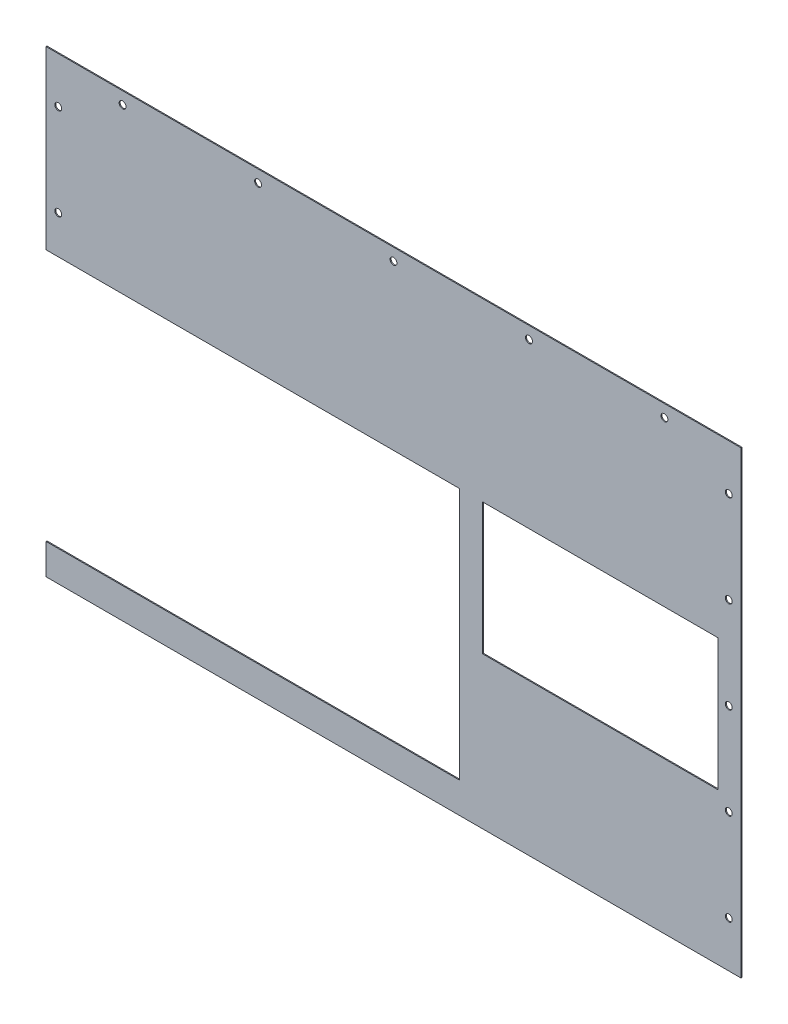
SolidWorks part; units mm, degrees
ref_plane "前视" through (0, 0, 0) normal (0, 0, 1) x (1, 0, 0)
ref_plane "上视" through (0, 0, 0) normal (0, 1, 0) x (1, 0, 0)
ref_plane "右视" through (0, 0, 0) normal (1, 0, 0) x (0, 0, -1)
sketch "Sketch1" plane through (0, 0, 0) normal (0, 0, 1) x (1, 0, 0)
  line L0 (-283.6006, 74.8867) -> (-13.6006, 74.8867)
  line L1 (-283.6006, 189.8867) -> (170.3994, 189.8867)
  line L2 (-283.6006, 189.8867) -> (-283.6006, -110.1133)
  line L3 (-283.6006, -110.1133) -> (170.3994, -110.1133)
  line L4 (170.3994, 189.8867) -> (170.3994, -110.1133)
  line L5 (-13.6006, -90.1133) -> (-283.6006, -90.1133)
  line L6 (-13.6006, 74.8867) -> (-13.6006, -90.1133)
  line L8 (1.3994, 74.8867) -> (155.3994, 74.8867)
  line L9 (1.3994, 74.8867) -> (1.3994, -11.1133)
  line L10 (1.3994, -11.1133) -> (155.3994, -11.1133)
  line L11 (155.3994, 74.8867) -> (155.3994, -11.1133)
  point P4 (-283.6006, 74.8867)
  point P5 (-283.6006, -90.1133)
  dimension "D1" = 300
  dimension "D2" = 454
  dimension "D3" = 115
  dimension "D4" = 20
  dimension "D5" = 270
  dimension "D6" = 154
  dimension "D7" = 86
  dimension "D8" = 15
  dimension "D9" = 15
  dimension "D10" = 115
sketch3d "3DSketch2" [suppressed]
  line L0 (-283.6006, 189.8867, 0) -> (-283.6006, 189.8867, -320)
  line L1 (-283.6006, 189.8867, 0) -> (170.3994, 189.8867, 0)
  line L2 (-283.6006, 189.8867, 0) -> (-283.6006, -160.1133, 0)
  line L3 (-283.6006, -160.1133, 0) -> (170.3994, -160.1133, 0)
  line L4 (170.3994, 189.8867, 0) -> (170.3994, -160.1133, 0)
  line L5 (-283.6006, 74.8867, 0) -> (-13.6006, 74.8867, 0)
  line L6 (-283.6006, 74.8867, 0) -> (-283.6006, -45.1133, 0)
  line L7 (-283.6006, -45.1133, 0) -> (-13.6006, -45.1133, 0)
  line L8 (-13.6006, 74.8867, 0) -> (-13.6006, -45.1133, 0)
  line L9 (1.3994, 74.8867, 0) -> (155.3994, 74.8867, 0)
  line L10 (1.3994, 74.8867, 0) -> (1.3994, -11.1133, 0)
  line L11 (1.3994, -11.1133, 0) -> (155.3994, -11.1133, 0)
  line L12 (155.3994, 74.8867, 0) -> (155.3994, -11.1133, 0)
  line L13 (170.3994, 189.8867, 0) -> (170.3994, 189.8867, -320)
  line L14 (170.3994, 189.8867, 0) -> (170.3994, -160.1133, 0)
  line L15 (-283.6006, 189.8867, -320) -> (170.3994, 189.8867, -320)
  dimension "D1" = 320
  dimension "D2" = 320
extrude "Boss-Extrude1" add sketch "Sketch1" along normal blind 0.635 contours L0 L6 L5 L2 L3 L4 L1 L8 L11 L10 L9 region at (-278.159, 132.3867, 0)
sketch "Sketch2" plane through (0, 0, 0) normal (0, 0, 1) x (1, 0, 0)
  line L2 (-283.6006, 189.8867) -> (-283.6006, 74.8867) construction
  line L3 (-283.6006, 189.8867) -> (170.3994, 189.8867) construction
  circle A0 centre (-233.6006, 181.9117) radius 2.248
  point P0 (-233.6006, 181.9117)
  dimension "D3" = 4.496
  dimension "D1" = 50
  dimension "D2" = 7.975
ref_axis "Axis1" through (-56.6006, 189.8867, 0) along (0, -1, 0)
extrude "Cut-Extrude3" cut sketch "Sketch2" along direction (0, 0, 1) on the side of the normal through all
ref_plane "Plane1" through (-56.6006, 0, 0) normal (-1, 0, 0) x (0, 0, 1)
ref_plane "Plane3" through (0, 39.8867, 0) normal (0, -1, 0) x (-1, 0, 0)
pattern_linear "LPattern1" count 5 spacing 88.5 along (1, 0, 0) of "Cut-Extrude3"
sketch "Sketch3" plane through (0, 0, 0) normal (0, 0, 1) x (1, 0, 0)
  line L0 (-283.6006, 189.8867) -> (-283.6006, 74.8867) construction
  line L1 (-283.6006, 189.8867) -> (170.3994, 189.8867) construction
  circle A0 centre (-275.6256, 159.8867) radius 2.248
  point P0 (-275.6256, 159.8867)
  dimension "D3" = 4.496
  dimension "D1" = 7.975
  dimension "D2" = 30
extrude "Cut-Extrude5" cut sketch "Sketch3" along normal through all
pattern_linear "LPattern2" count 6 spacing 60 along (0, -1, 0) of "Cut-Extrude5"
mirror "Mirror1" about plane through (-56.6006, 0, 0) normal (-1, 0, 0) of "LPattern2"
